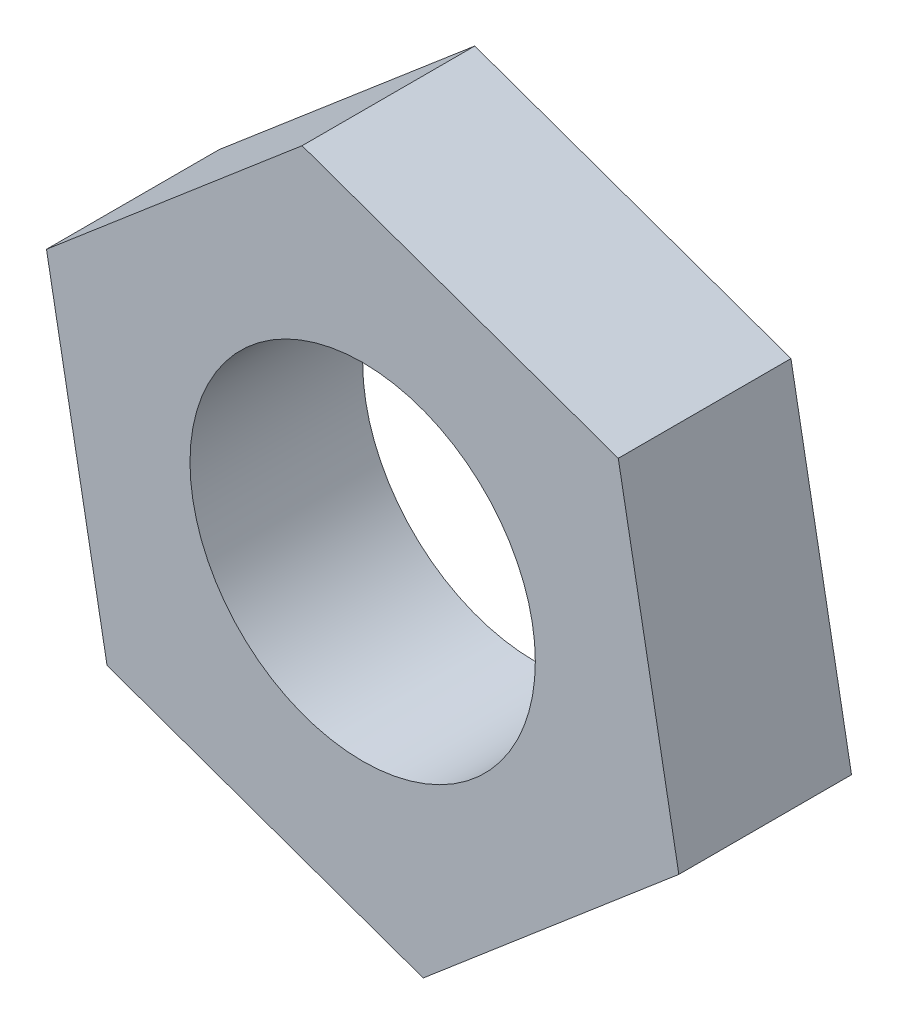
SolidWorks part; units mm, degrees
ref_plane "Front Plane" through (0, 0, 0) normal (0, 0, 1) x (1, 0, 0)
ref_plane "Top Plane" through (0, 0, 0) normal (0, 1, 0) x (1, 0, 0)
ref_plane "Right Plane" through (0, 0, 0) normal (1, 0, 0) x (0, 0, -1)
sketch "Sketch1" plane through (0, 0, 0) normal (0, 0, 1) x (1, 0, 0)
  line L1 (1324.4991, -1696.9218) -> (1328.9401, -1693.1429)
  line L2 (1328.9401, -1693.1429) -> (1327.8881, -1687.4074)
  line L3 (1327.8881, -1687.4074) -> (1322.3949, -1685.4507)
  line L4 (1322.3949, -1685.4507) -> (1317.9538, -1689.2296)
  line L5 (1317.9538, -1689.2296) -> (1319.0059, -1694.9652)
  line L6 (1324.1558, -1686.1863) -> (1322.7382, -1686.1863)
  line L7 (1319.4713, -1688.0724) -> (1318.7625, -1689.3001)
  line L8 (1318.7625, -1693.0724) -> (1319.4713, -1694.3001)
  line L9 (1322.7382, -1696.1863) -> (1324.1558, -1696.1863)
  line L10 (1327.4227, -1694.3001) -> (1328.1315, -1693.0724)
  line L11 (1328.1315, -1689.3001) -> (1327.4227, -1688.0724)
  line L12 (1324.1558, -1686.1863) -> (1322.7382, -1686.1863)
  line L13 (1319.4713, -1688.0724) -> (1318.7625, -1689.3001)
  line L14 (1318.7625, -1693.0724) -> (1319.4713, -1694.3001)
  line L15 (1322.7382, -1696.1863) -> (1324.1558, -1696.1863)
  line L16 (1327.4227, -1694.3001) -> (1328.1315, -1693.0724)
  line L17 (1328.1315, -1689.3001) -> (1327.4227, -1688.0724)
  line L18 (1319.0059, -1694.9652) -> (1324.4991, -1696.9218)
  arc A0 (1327.4227, -1688.0724) -> (1324.1558, -1686.1863) centre (1323.447, -1691.1863) ccw
  arc A1 (1322.7382, -1686.1863) -> (1319.4713, -1688.0724) centre (1323.447, -1691.1863) ccw
  arc A2 (1318.7625, -1689.3001) -> (1318.7625, -1693.0724) centre (1323.447, -1691.1863) ccw
  arc A3 (1319.4713, -1694.3001) -> (1322.7382, -1696.1863) centre (1323.447, -1691.1863) ccw
  arc A4 (1324.1558, -1696.1863) -> (1327.4227, -1694.3001) centre (1323.447, -1691.1863) ccw
  arc A5 (1328.1315, -1693.0724) -> (1328.1315, -1689.3001) centre (1323.447, -1691.1863) ccw
  arc A6 (1327.4227, -1688.0724) -> (1324.1558, -1686.1863) centre (1323.447, -1691.1863) ccw
  arc A7 (1322.7382, -1686.1863) -> (1319.4713, -1688.0724) centre (1323.447, -1691.1863) ccw
  arc A8 (1318.7625, -1689.3001) -> (1318.7625, -1693.0724) centre (1323.447, -1691.1863) ccw
  arc A9 (1319.4713, -1694.3001) -> (1322.7382, -1696.1863) centre (1323.447, -1691.1863) ccw
  arc A10 (1324.1558, -1696.1863) -> (1327.4227, -1694.3001) centre (1323.447, -1691.1863) ccw
  arc A11 (1328.1315, -1693.0724) -> (1328.1315, -1689.3001) centre (1323.447, -1691.1863) ccw
  circle A12 centre (1323.447, -1691.1863) radius 5.05 construction
  circle A13 centre (1323.447, -1691.1863) radius 3
  dimension "D2" = 6
  dimension "D1" = 0
extrude "Boss-Extrude1" add sketch "Sketch1" along normal blind 3 contours A11 L17 A6 L12 A7 L13 A8 L14 A9 L15 A10 L16 A13 | A10 L15 A9 L18 L1 | A11 L16 A10 L1 L2 | A11 L2 L3 A6 L17 | A7 L12 A6 L3 L4 | A8 L13 A7 L4 L5 | A9 L14 A8 L5 L18 region at (1324.3573, -1696.3163, 0) region at (1328.3449, -1692.9629, 0) region at (1325.4613, -1695.6617, 0) region at (1319.4594, -1694.5396, 0) region at (1327.4346, -1687.8329, 0) region at (1318.5491, -1689.4096, 0) region at (1322.5367, -1686.0562, 0)
